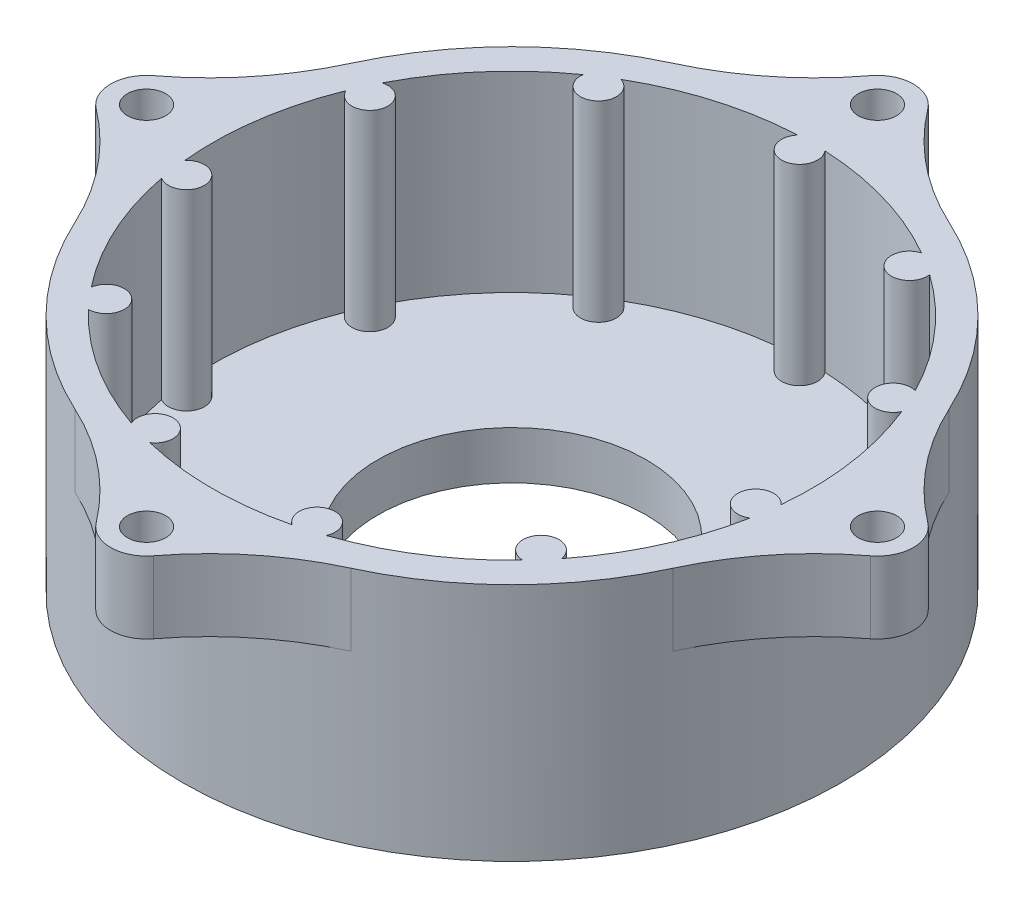
SolidWorks part; units mm, degrees
ref_plane "Front Plane" through (0, 0, 0) normal (0, 0, 1) x (1, 0, 0)
ref_plane "Top Plane" through (0, 0, 0) normal (0, 1, 0) x (1, 0, 0)
ref_plane "Right Plane" through (0, 0, 0) normal (1, 0, 0) x (0, 0, -1)
sketch "Sketch1" plane through (0, 0, 0) normal (0, 1, 0) x (1, 0, 0)
  line L0 (0, 0) -> (0, 24) construction
  line L1 (0, 0) -> (-15.5, 0) construction
  line L2 (-15.5, 0) -> (-15.5, 15.5) construction
  circle A0 centre (0, 0) radius 27.5
  circle A1 centre (0, 24) radius 1.5
  circle A2 centre (12.9754, 20.1901) radius 1.5
  circle A3 centre (21.8312, 9.97) radius 1.5
  circle A4 centre (23.7557, -3.4156) radius 1.5
  circle A5 centre (18.138, -15.7167) radius 1.5
  circle A6 centre (6.7616, -23.0278) radius 1.5
  circle A7 centre (-6.7616, -23.0278) radius 1.5
  circle A8 centre (-18.138, -15.7167) radius 1.5
  circle A9 centre (-23.7557, -3.4156) radius 1.5
  circle A10 centre (-21.8312, 9.97) radius 1.5
  circle A11 centre (-12.9754, 20.1901) radius 1.5
  circle A12 centre (0, 0) radius 25
  circle A13 centre (0, 0) radius 11.2
  point P27 (0, 0)
  dimension "D1" = 55
  dimension "D4" = 3
  dimension "D6" = 50
  dimension "D7" = 22.4
  dimension "D2" = 24
  dimension "D3" = 24
  dimension "D8" = 15.5
  dimension "D5" = 11
extrude "Boss-Extrude1" add sketch "Sketch1" along normal blind 16 contours A0 A12 A6 A7 A8 A9 A10 A11 A1 A2 A3 A4 A5 | A10 A12 | A11 A12 | A1 A12 | A2 A12 | A3 A12 | A4 A12 | A5 A12 | A6 A12 | A7 A12 | A8 A12 | A9 A12 | A12 A10 | A12 A9 | A12 A8 | A12 A7 | A12 A6 | A12 A5 | A12 A3 | A12 A2 | A12 A1 | A12 A11 | A11 | A4 region at (-26.7222, 0, 0) region at (0, 0, -23.8485) region at (0, 0, -25.1981) region at (12.8935, 0, -20.0626) region at (13.6231, 0, -21.198) region at (-13.6231, 0, -21.198) region at (-12.8935, 0, -20.0626) region at (21.6933, 0, -9.907) region at (22.921, 0, -10.4677) region at (-22.921, 0, -10.4677) region at (-21.6933, 0, -9.907) region at (-24.9416, 0, 3.5861) region at (-23.6057, 0, 3.394) region at (23.6057, 0, 3.394) region at (-19.0434, 0, 16.5012) region at (-18.0235, 0, 15.6174) region at (18.0235, 0, 15.6174) region at (19.0434, 0, 16.5012) region at (-7.0991, 0, 24.1774) region at (-6.7189, 0, 22.8825) region at (6.7189, 0, 22.8825) region at (7.0991, 0, 24.1774)
extrude "Boss-Extrude2" add sketch "Sketch1<3>" against normal blind 4 contours A0
sketch "Sketch1<3>" plane through (0, 0, 0) normal (0, 1, 0) x (1, 0, 0) same geometry as "Sketch1"
extrude "Cut-Extrude1" cut sketch "Sketch1<5>" against normal through all both and the other way through all contours A13 region at (0, 0, 0)
sketch "Sketch1<5>" plane through (0, 0, 0) normal (0, 1, 0) x (1, 0, 0) same geometry as "Sketch1"
ref_plane "Plane1" through (0, 10, 0) normal (0, 1, 0) x (1, 0, 0)
sketch "Sketch6" plane through (0, 10, 0) normal (0, 1, 0) x (1, 0, 0)
  circle A10 centre (0, 30.5) radius 3
  circle A11 centre (30.5, 0) radius 3
  circle A12 centre (0, -30.5) radius 3
  circle A13 centre (-30.5, 0) radius 3
  circle A14 centre (0, 0) radius 27.5 construction
  circle A15 centre (0, 0) radius 27.5
  circle A16 centre (0, 30.5) radius 1.6
  circle A17 centre (30.5, 0) radius 1.6
  circle A18 centre (0, -30.5) radius 1.6
  circle A19 centre (-30.5, 0) radius 1.6
  point P12 (0, 0)
  point P14 (0, 0)
  point P22 (0, 0)
  point P26 (0, 0)
  dimension "D2" = 6
  dimension "D1" = 4
  dimension "D3" = 3.2
  dimension "D4" = 4
extrude "Boss-Extrude6" add sketch "Sketch6" along normal up to surface (6 mm away) separate body contours A13 A19 | A10 A16 | A11 A17 | A12 A18 region at (2.0613, 10, -28.4387) region at (30.5, 10, -2.9151) region at (2.0613, 10, 28.4387) region at (-33.4151, 10, 0) up to face at (0, 16, 0)
sketch "Sketch8" plane through (0, 16, 0) normal (0, 1, 0) x (1, 0, 0)
  line L0 (-30.5, 0) -> (-32.3117, -2.3912) construction
  line L1 (0, 0) -> (-6.155, 0) construction
  circle A0 centre (-30.5, 0) radius 3 construction
  arc A1 (-32.3117, -2.3912) -> (-24.9715, -11.5184) centre (-46.8847, -21.626) cw
  circle A2 centre (0, 0) radius 27.5 construction
  arc A3 (-32.3117, 2.3912) -> (-24.9715, 11.5184) centre (-46.8847, 21.626) ccw
  arc A4 (-32.3117, 2.3912) -> (-32.3117, -2.3912) centre (-30.5, 0) ccw
  arc A5 (-24.9715, 11.5184) -> (-24.9715, -11.5184) centre (0, 0) ccw
  circle A6 centre (-30.5, 0) radius 1.6
  arc A7 (-2.3912, 32.3117) -> (-11.5184, 24.9715) centre (-21.626, 46.8847) cw
  arc A8 (2.3912, 32.3117) -> (-2.3912, 32.3117) centre (0, 30.5) ccw
  arc A9 (2.3912, 32.3117) -> (11.5184, 24.9715) centre (21.626, 46.8847) ccw
  arc A10 (11.5184, 24.9715) -> (-11.5184, 24.9715) centre (0, 0) ccw
  circle A11 centre (0, 30.5) radius 1.6
  arc A12 (32.3117, 2.3912) -> (24.9715, 11.5184) centre (46.8847, 21.626) cw
  arc A13 (32.3117, -2.3912) -> (32.3117, 2.3912) centre (30.5, 0) ccw
  arc A14 (32.3117, -2.3912) -> (24.9715, -11.5184) centre (46.8847, -21.626) ccw
  arc A15 (24.9715, -11.5184) -> (24.9715, 11.5184) centre (0, 0) ccw
  circle A16 centre (30.5, 0) radius 1.6
  arc A17 (2.3912, -32.3117) -> (11.5184, -24.9715) centre (21.626, -46.8847) cw
  arc A18 (-2.3912, -32.3117) -> (2.3912, -32.3117) centre (0, -30.5) ccw
  arc A19 (-2.3912, -32.3117) -> (-11.5184, -24.9715) centre (-21.626, -46.8847) ccw
  arc A20 (-11.5184, -24.9715) -> (11.5184, -24.9715) centre (0, 0) ccw
  circle A21 centre (0, -30.5) radius 1.6
  point P46 (0, 0)
  dimension "D1" = 4
extrude "Boss-Extrude8" add sketch "Sketch8" against normal up to surface (6 mm away) up to face at (-30.5, 10, 1.6)
